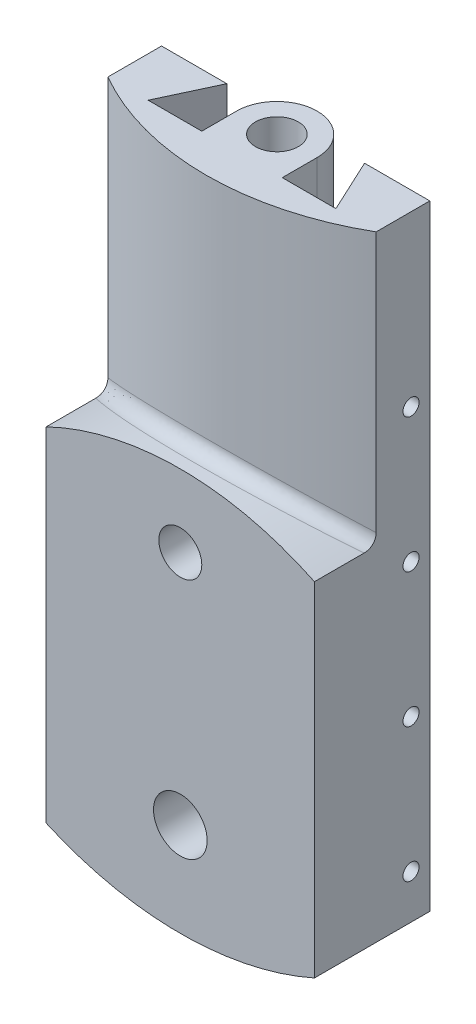
SolidWorks part; units mm, degrees
ref_plane "Front Plane" through (0, 0, 0) normal (0, 0, 1) x (1, 0, 0)
ref_plane "Top Plane" through (0, 0, 0) normal (0, 1, 0) x (1, 0, 0)
ref_plane "Right Plane" through (0, 0, 0) normal (1, 0, 0) x (0, 0, -1)
sketch "Sketch1" plane through (0, 0, 0) normal (0, 1, 0) x (1, 0, 0)
  line L0 (-50, 13.3975) -> (-50, 33.3975)
  line L1 (-50, 33.3975) -> (-25.6738, 33.3975)
  line L2 (-25.6738, 33.3975) -> (-35, 13.3975)
  line L3 (-35, 13.3975) -> (35, 13.3975)
  line L4 (35, 13.3975) -> (25.6738, 33.3975)
  line L5 (25.6738, 33.3975) -> (50, 33.3975)
  line L6 (50, 33.3975) -> (50, 13.3975)
  arc A0 (-50, 13.3975) -> (50, 13.3975) centre (0, 100) ccw
  point P3 (0, 0)
  point P5 (32.0965, 13.3975)
  point P12 (0, 13.3975)
  dimension "D1" = 100
  dimension "D2" = 20
  dimension "D3" = 70
  dimension "D4" = 65
  dimension "D5" = 65
  dimension "D6" = 100
extrude "Boss-Extrude1" add sketch "Sketch1" against normal blind 240
sketch "Sketch2" plane through (0, 0, 0) normal (0, 0, 1) x (1, 0, 0)
  line L0 (-50, -240) -> (-50, 0) construction
  line L1 (50, -240) -> (50, 0) construction
  line L2 (-50, -240) -> (50, -240) construction
  line L3 (50, -229.3788) -> (50, -101.4384)
  line L4 (-50, -229.3788) -> (-50, -101.4384)
  arc A0 (-50, -101.4384) -> (50, -101.4384) centre (0, -205) cw
  arc A1 (-50, -229.3788) -> (50, -229.3788) centre (0, -117) ccw
  point P10 (0, -240)
  point P13 (0, 0)
  point P14 (0, 0)
  point P15 (-86.657, -146.3728)
  point P16 (0, 0)
  dimension "D1" = 123
  dimension "D2" = 115
  dimension "D4" = 35
extrude "Boss-Extrude2" add sketch "Sketch2" along normal blind 23 from surface starting at face at (0, -120, -13.3975)
sketch "Sketch4" plane through (0, 0, 9.6025) normal (0, 0, 1) x (1, 0, 0)
  line L0 (-50, -229.3788) -> (-50, -240) construction
  line L1 (-50, -240) -> (0, -240) construction
  line L2 (0, -240) -> (50, -240) construction
  line L3 (50, -240) -> (50, -229.3788) construction
  line L4 (-50, -229.3788) -> (-50, -240)
  line L5 (-50, -240) -> (0, -240)
  line L6 (0, -240) -> (50, -240)
  line L7 (50, -240) -> (50, -229.3788)
  arc A0 (-50, -229.3788) -> (0, -240) centre (0, -117) ccw construction
  arc A1 (0, -240) -> (50, -229.3788) centre (0, -117) ccw construction
  arc A2 (-50, -229.3788) -> (0, -240) centre (0, -117) ccw
  arc A3 (0, -240) -> (50, -229.3788) centre (0, -117) ccw
  arc M2 (-50, -229.3788) -> (50, -229.3788) centre (0, -117) ccw
extrude "Cut-Extrude1" cut sketch "Sketch4" against normal up to next contours L6 L7 M2 | L4 L5 M2 region at (-37.6105, -236.8387, 9.6025) region at (37.6105, -236.8387, 9.6025)
sketch "Sketch6" plane through (0, 0, 0) normal (0, 1, 0) x (1, 0, 0)
  line L0 (-50, -9.6025) -> (50, -9.6025) construction
  line L1 (-15, 26.3975) -> (-15, 11.3975)
  line L3 (15, 26.3975) -> (15, 11.3975)
  line L4 (-15, 11.3975) -> (15, 11.3975)
  arc A0 (15, 26.3975) -> (-15, 26.3975) centre (0, 26.3975) ccw
  circle A1 centre (0, 26.3975) radius 8
  point P8 (0, 11.3975)
  dimension "D1" = 30
  dimension "D3" = 16
  dimension "D2" = 36
  dimension "D4" = 15
extrude "Boss-Extrude3" add sketch "Sketch6" against normal blind 25
sketch "Sketch7" plane through (50, 0, 0) normal (1, 0, 0) x (0, 0, -1)
  line L0 (41.3975, 0) -> (26.3975, 0) construction
  line L1 (41.3975, -25) -> (41.3975, 0) construction
  circle A0 centre (26.3975, -213) radius 3
  circle A1 centre (26.3975, -163) radius 3
  circle A2 centre (26.3975, -113) radius 3
  circle A3 centre (26.3975, -63) radius 3
  point P8 (0, 0)
  dimension "D1" = 6
  dimension "D2" = 63
  dimension "D3" = 50
  dimension "D4" = 50
  dimension "D5" = 50
  dimension "D6" = 15
extrude "Cut-Extrude2" cut sketch "Sketch7" against normal through all
sketch "Sketch8" plane through (0, 0, 9.6025) normal (0, 0, 1) x (1, 0, 0)
  circle A0 centre (0, -205) radius 10
  circle A1 centre (0, -117) radius 8
  arc A2 (-50, -229.3788) -> (50, -229.3788) centre (0, -117) ccw construction
  point P7 (0, -240)
  point P8 (0, 0)
  point P9 (0, 0)
  dimension "D1" = 35
  dimension "D3" = 20
  dimension "D4" = 16
  dimension "D2" = 123
extrude "Cut-Extrude3" cut sketch "Sketch8" against normal through all
fillet "Fillet1" radius 5 1 edges at (-2.8187, -90.0345, -0.0397)
